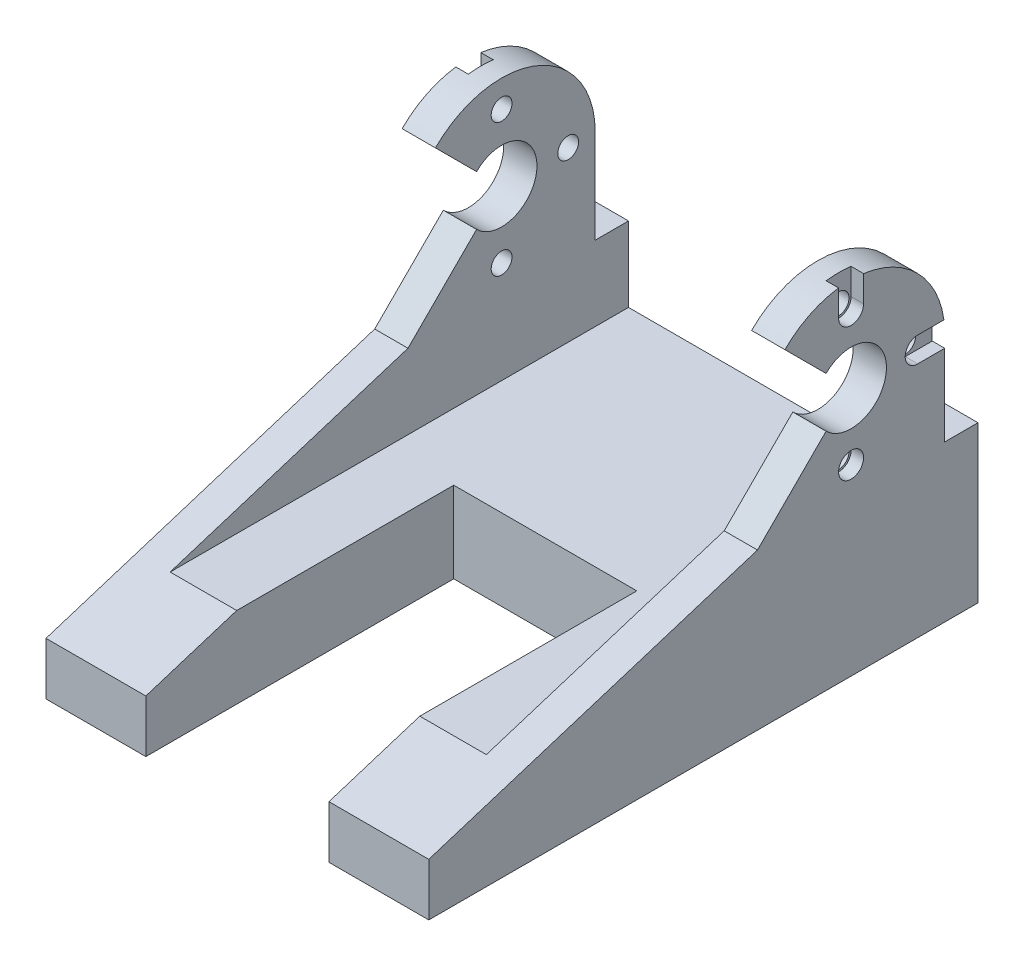
SolidWorks part; units mm, degrees
ref_plane "Front Plane" through (0, 0, 0) normal (0, 0, 1) x (1, 0, 0)
ref_plane "Top Plane" through (0, 0, 0) normal (0, 1, 0) x (1, 0, 0)
ref_plane "Right Plane" through (0, 0, 0) normal (1, 0, 0) x (0, 0, -1)
sketch "Sketch1" plane through (0, 0, 0) normal (0, 0, 1) x (1, 0, 0)
  line L1 (-25, 0) -> (25, 0)
  line L2 (-25, 0) -> (-25, -170)
  line L3 (-25, -170) -> (25, -170)
  line L4 (25, 0) -> (25, -170)
  dimension "D1" = 170
  dimension "D2" = 50
extrude "Boss-Extrude1" add sketch "Sketch1" against normal blind 55
sketch "Sketch2" plane through (0, 0, 0) normal (0, 0, 1) x (1, 0, 0)
  line L0 (25, 0) -> (-25, 0) construction
  line L1 (-17, 0) -> (17, 0)
  line L2 (-17, 0) -> (-17, -27)
  line L3 (-17, -27) -> (17, -27)
  line L4 (17, 0) -> (17, -27)
  line L5 (-25, 0) -> (-25, -170) construction
  dimension "D1" = 8
  dimension "D2" = 34
  dimension "D3" = 27
extrude "Cut-Extrude1" cut sketch "Sketch2" against normal through all
sketch "Sketch3" plane through (25, 0, 0) normal (1, 0, 0) x (0, 0, -1)
  line L0 (0, -170) -> (0, 0) construction
  line L1 (55, -27) -> (0, -27)
  line L2 (55, -27) -> (55, -24)
  line L3 (55, -24) -> (0, -24)
  line L4 (0, -27) -> (0, -24)
  line L5 (55, -170) -> (55, 0) construction
  line L7 (0, 0) -> (10, 0)
  line L8 (0, 0) -> (0, -24)
  line L9 (0, -24) -> (10, -24)
  line L10 (10, 0) -> (10, -24)
  line L11 (55, 0) -> (45, 0)
  line L12 (55, 0) -> (55, -24)
  line L13 (55, -24) -> (45, -24)
  line L14 (45, 0) -> (45, -24)
  circle A0 centre (27.5, -12.75) radius 10.25
  circle A1 centre (27.5, -12.75) radius 4.25
  circle A2 centre (27.5, -12.75) radius 8
  circle A3 centre (27.5, -4.75) radius 1
  circle A4 centre (35.5, -12.75) radius 1
  circle A5 centre (27.5, -20.75) radius 1
  circle A6 centre (19.5, -12.75) radius 1
  point P32 (27.5, -12.75)
  line M7 (0, 0) -> (0, -170)
  line M9 (55, -170) -> (55, 0)
  line M10 (55, 0) -> (0, 0)
  dimension "D2" = 11.25
  dimension "D3" = 27.5
  dimension "D4" = 20.5
  dimension "D7" = 8.5
  dimension "D8" = 16
  dimension "D9" = 4
  dimension "D1" = 3
  dimension "D5" = 10
  dimension "D6" = 10
extrude "Cut-Extrude2" cut sketch "Sketch3" against normal through all contours L14 L3 M10 M9 | L10 L3 M10 M7 | A2 A6 | A2 A6 | A1 | A2 A5 | A2 A5 | A2 A4 | A2 A4 | A2 A3 | A2 A3 region at (25, -12, -50) region at (25, -12, -5) region at (25, -12.75, -27.5) region at (25, -12.75, -35.0645) region at (25, -12.75, -35.913) region at (25, -5.1855, -27.5) region at (25, -4.337, -27.5) region at (25, -21.163, -27.5) region at (25, -20.3145, -27.5) region at (25, -12.75, -19.9355) region at (25, -12.75, -19.087)
sketch "Sketch4" plane through (0, 0, -10) normal (0, 0, 1) x (1, 0, 0)
  line L0 (-25, -24) -> (-17, -24) construction
  line L1 (-17, 0) -> (-19, 0)
  line L2 (-17, 0) -> (-17, -24)
  line L3 (-17, -24) -> (-19, -24)
  line L4 (-19, 0) -> (-19, -24)
  line L5 (0, 0) -> (0, -13.53) construction
  line L6 (19, 0) -> (19, -24)
  line L7 (17, -24) -> (19, -24)
  line L8 (17, 0) -> (17, -24)
  line L9 (17, 0) -> (19, 0)
  dimension "D1" = 2
extrude "Cut-Extrude3" cut sketch "Sketch4" against normal through all
sketch "Sketch5" plane through (25, 0, 0) normal (1, 0, 0) x (0, 0, -1)
  line L1 (10, 0) -> (45, 0)
  line L2 (10, 0) -> (10, -24)
  line L3 (10, -24) -> (45, -24)
  line L4 (45, 0) -> (45, -24)
  line L5 (38.75, -12.75) -> (38.75, -24)
  line L6 (16.25, -12.75) -> (10, -12.75)
  line L7 (16.25, -12.75) -> (16.25, -24)
  line L8 (16.25, -24) -> (10, -24)
  line L9 (10, -12.75) -> (10, -24)
  line L10 (38.75, -12.75) -> (45, -12.75)
  line L11 (38.75, -12.75) -> (38.75, -24)
  line L12 (38.75, -24) -> (45, -24)
  line L13 (45, -12.75) -> (45, -24)
  circle A0 centre (27.5, -12.75) radius 11.25
  line M8 (45, -24) -> (45, 0)
  line M9 (45, 0) -> (10, 0)
  line M10 (10, 0) -> (10, -24)
  dimension "D1" = 22.5
extrude "Cut-Extrude4" cut sketch "Sketch5" against normal through all contours A0 L10 L4 L6 M9 M10 | L7 L6 L2 L3 | L10 L5 L3 M8 region at (25, -0.3725, -27.5) region at (25, -18.375, -13.125) region at (25, -18.375, -41.875)
sketch "Sketch6" plane through (0, 0, 0) normal (0, 0, 1) x (1, 0, 0)
  line L1 (-19, -24) -> (19, -24)
  line L2 (-19, -24) -> (-19, -34)
  line L3 (-19, -34) -> (19, -34)
  line L4 (19, -24) -> (19, -34)
  dimension "D1" = 10
extrude "Cut-Extrude5" cut sketch "Sketch6" against normal through all
sketch "Sketch8" plane through (25, 0, 0) normal (1, 0, 0) x (0, 0, -1)
  line L0 (55, -170) -> (55, -24) construction
  line L1 (0, -170) -> (0, -24) construction
  line L2 (41.75, -132.5) -> (13.25, -132.5)
  line L3 (27.5, -132.5) -> (27.5, -179)
  line L4 (41.75, -179) -> (13.25, -179)
  line L5 (13.25, -132.5) -> (13.25, -179)
  line L7 (41.75, -132.5) -> (41.75, -179)
  line L11 (27.5, -167.75) -> (55, -167.75)
  line L12 (27.5, -167.75) -> (27.5, -170)
  line L13 (27.5, -170) -> (55, -170)
  line L14 (55, -167.75) -> (55, -170)
  line L16 (27.5, -167.75) -> (0, -167.75)
  line L17 (27.5, -167.75) -> (27.5, -170)
  line L18 (27.5, -170) -> (0, -170)
  line L19 (0, -167.75) -> (0, -170)
  circle A0 centre (27.5, -167.75) radius 10.25
  circle A1 centre (27.5, -12.75) radius 10.25
  line M4 (0, -24) -> (0, -170)
  line M5 (0, -170) -> (55, -170)
  line M6 (55, -170) -> (55, -24)
  dimension "D1" = 27.5
  dimension "D2" = 20.5
  dimension "D3" = 155
  dimension "D4" = 14.25
  dimension "D5" = 11.25
  dimension "D6" = 46.5
  dimension "D7" = 13.25
extrude "Cut-Extrude7" cut sketch "Sketch8" against normal through all contours A0 L3 L2 L5 L16 | A0 L11 L7 L2 L3 | L11 L7 M5 M6 | L5 L16 M4 M5 | A0 L16 L5 M5 | A0 L13 L7 L11 | L3 A0 L16 | L11 A0 L3 | L16 A0 L18 L3 | A0 L11 L3 M5 region at (25, -147.5157, -35.1704) region at (25, -147.5157, -19.8296) region at (25, -168.875, -48.375) region at (25, -168.8865, -39.7079) region at (25, -163.3998, -31.8502) region at (25, -163.3998, -23.1498) region at (25, -168.8704, -32.5838) region at (25, -168.8865, -15.2921) region at (25, -168.875, -6.625) region at (25, -168.8704, -22.4162)
sketch "Sketch9" plane through (0, 0, 0) normal (0, 0, 1) x (1, 0, 0)
  line L0 (-25, -167.75) -> (25, -167.75) construction
  line L1 (17, -167.75) -> (-17, -167.75)
  line L2 (17, -167.75) -> (17, -132.5)
  line L3 (17, -132.5) -> (-17, -132.5)
  line L4 (-17, -167.75) -> (-17, -132.5)
  line L5 (-25, -132.5) -> (25, -132.5) construction
  line L7 (-25, -24) -> (-25, -167.75) construction
  line L9 (25, -167.75) -> (25, -24) construction
  dimension "D1" = 8
  dimension "D2" = 8
extrude "Cut-Extrude8" cut sketch "Sketch9" against normal through all
sketch "Sketch11" plane through (25, 0, 0) normal (1, 0, 0) x (0, 0, -1)
  line L0 (27.5, -157.5) -> (27.5, -147.5)
  line L2 (27.5, -147.5) -> (55, -147.5)
  line L3 (27.5, -147.5) -> (27.5, -167.75)
  line L4 (27.5, -167.75) -> (55, -167.75)
  line L5 (55, -147.5) -> (55, -167.75)
  line L6 (27.5, -147.5) -> (0, -147.5)
  line L7 (27.5, -147.5) -> (27.5, -167.75)
  line L8 (27.5, -167.75) -> (0, -167.75)
  line L9 (0, -147.5) -> (0, -167.75)
  circle A0 centre (27.5, -167.75) radius 10.25
  arc A1 (38.75, -12.75) -> (16.25, -12.75) centre (27.5, -12.75) ccw construction
  line M1 (0, -167.75) -> (13.25, -167.75)
  line M2 (13.25, -167.75) -> (13.25, -132.5)
  line M4 (41.75, -132.5) -> (41.75, -167.75)
  line M5 (41.75, -167.75) -> (55, -167.75)
  line M6 (55, -167.75) -> (55, -24)
  line M12 (0, -24) -> (0, -167.75)
  dimension "D1" = 155
  dimension "D2" = 20.5
  dimension "D3" = 10
extrude "Cut-Extrude9" cut sketch "Sketch11" against normal through all contours A0 L0 L6 L8 M2 | A0 L4 L2 L0 M4 | L2 M4 M5 M6 | L6 M2 M12 M1 region at (25, -155.3124, -19.2638) region at (25, -155.3124, -35.7362) region at (25, -157.625, -48.375) region at (25, -157.625, -6.625)
sketch "Sketch12" plane through (25, 0, 0) normal (1, 0, 0) x (0, 0, -1)
  line L1 (13.25, -132.5) -> (41.75, -132.5)
  line L2 (13.25, -132.5) -> (13.25, -147.5)
  line L3 (13.25, -147.5) -> (41.75, -147.5)
  line L4 (41.75, -132.5) -> (41.75, -147.5)
extrude "Boss-Extrude2" add sketch "Sketch12" against normal blind 8
ref_plane "Plane1" through (0, 0, 0) normal (1, 0, 0) x (0, 0, -1)
mirror "Mirror1" about plane through (0, 0, 0) normal (1, 0, 0) of "Boss-Extrude2"
sketch "Sketch14" plane through (0, 0, 0) normal (0, 0, 1) x (1, 0, 0)
  line L0 (17, -148.55) -> (17, -158.75) construction
  line L1 (-17, -132.5) -> (17, -132.5)
  line L2 (-17, -132.5) -> (-17, -147.5)
  line L3 (-17, -147.5) -> (17, -147.5)
  line L4 (17, -132.5) -> (17, -147.5)
  line L5 (-17, -147.5) -> (17, -147.5)
  line L6 (-17, -147.5) -> (-17, -157.75)
  line L7 (-17, -157.75) -> (17, -157.75)
  line L8 (17, -147.5) -> (17, -157.75)
  line M11 (-17, -147.5) -> (-17, -132.5)
  line M12 (-17, -132.5) -> (17, -132.5)
  line M13 (17, -132.5) -> (17, -147.5)
  dimension "D1" = 10.25
extrude "Boss-Extrude3" add sketch "Sketch14" against normal blind 13.25 contours L3 M11 M13 M12 | L8 L3 L6 L7 region at (0, -140, 0) region at (0, -152.625, 0)
ref_plane "Plane2" through (0, 0, -27.5) normal (0, 0, 1) x (1, 0, 0)
mirror "Mirror2" about plane through (0, 0, -27.5) normal (0, 0, 1) of "Boss-Extrude3"
sketch "Sketch16" plane through (25, 0, 0) normal (1, 0, 0) x (0, 0, -1)
  line L0 (41.75, -132.5) -> (13.25, -132.5) construction
  line L1 (13.25, -132.5) -> (13.25, -147.5) construction
  circle A1 centre (16.5, -135.75) radius 2.5
  circle A2 centre (16.5, -135.75) radius 4.5
  circle A3 centre (38.5, -135.75) radius 4.5
  dimension "D1" = 3.25
  dimension "D2" = 3.25
  dimension "D3" = 2
extrude "Cut-Extrude13" cut sketch "Sketch16" against normal blind 8 contours A1 | A2 A1 | A3 region at (25, -135.75, -16.5) region at (25, -135.75, -12.1273) region at (25, -135.75, -38.5)
mirror "Mirror3" about plane through (0, 0, 0) normal (1, 0, 0) of "Cut-Extrude13"
sketch "Sketch17" plane through (25, 0, 0) normal (1, 0, 0) x (0, 0, -1)
  line L0 (55, -147.5) -> (55, -24) construction
  line L1 (27.5, -1.5) -> (55, -1.5)
  line L2 (27.5, -1.5) -> (27.5, -51.5)
  line L3 (27.5, -51.5) -> (55, -51.5)
  line L4 (55, -1.5) -> (55, -51.5)
  line L8 (55, -51.5) -> (0, -51.5)
  line L9 (55, -51.5) -> (55, -157.75)
  line L10 (55, -157.75) -> (0, -157.75)
  line L11 (0, -51.5) -> (0, -157.75)
  arc A0 (38.75, -12.75) -> (16.25, -12.75) centre (27.5, -12.75) ccw construction
  circle M2 centre (16.5, -135.75) radius 4.5
  circle M3 centre (38.5, -135.75) radius 4.5
  line M4 (0, -147.5) -> (55, -147.5)
  line M5 (55, -147.5) -> (55, -24)
  line M11 (0, -24) -> (0, -147.5)
  dimension "D1" = 50
extrude "Cut-Extrude15" cut sketch "Sketch17" against normal through all contours L3 L8 M11 M4 M5 M2 M3 | L11 L10 L9 M4 | M3 | M2 region at (25, -98.6049, -27.5) region at (25, -152.625, -27.5) region at (25, -135.75, -16.5) region at (25, -135.75, -38.5)
sketch "Sketch18" plane through (25, 0, 0) normal (1, 0, 0) x (0, 0, -1)
  line L1 (38.75, -24) -> (-71.25, -24)
  line L2 (38.75, -24) -> (38.75, -51.5)
  line L3 (38.75, -51.5) -> (-71.25, -51.5)
  line L4 (-71.25, -24) -> (-71.25, -51.5)
  line L6 (38.75, -24) -> (68.75, -24)
  line L7 (38.75, -24) -> (38.75, -51.5)
  line L8 (38.75, -51.5) -> (68.75, -51.5)
  line L9 (68.75, -24) -> (68.75, -51.5)
  line M8 (0, -24) -> (0, -51.5)
  line M9 (0, -51.5) -> (55, -51.5)
  line M10 (55, -51.5) -> (55, -24)
  line M11 (55, -24) -> (38.75, -24)
  line M15 (16.25, -24) -> (0, -24)
  dimension "D1" = 110
  dimension "D2" = 30
extrude "Boss-Extrude4" add sketch "Sketch18" against normal blind 50 contours L1 L4 L3 M8 | L9 L6 L8 M10 | L2 L1 M15 M8 M9 | L2 M11 M9 M10 region at (25, -37.75, -19.375) region at (25, -37.75, -46.875) region at (25, -37.75, -61.875) region at (25, -37.75, 35.625)
sketch "Sketch19" plane through (0, 0, 71.25) normal (0, 0, 1) x (1, 0, 0)
  line L1 (-19, -24) -> (19, -24)
  line L2 (-19, -24) -> (-19, -31)
  line L3 (-19, -31) -> (19, -31)
  line L4 (19, -24) -> (19, -31)
  dimension "D1" = 7
extrude "Cut-Extrude16" cut sketch "Sketch19" against normal through all
sketch "Sketch20" plane through (25, 0, 0) normal (1, 0, 0) x (0, 0, -1)
  line L1 (-71.25, -24) -> (68.75, -24)
  line L2 (-71.25, -24) -> (-71.25, -51.5)
  line L3 (-71.25, -51.5) -> (68.75, -51.5)
  line L4 (68.75, -24) -> (68.75, -51.5)
  line L5 (16.25, -24) -> (-13.75, -24)
  line L6 (16.25, -24) -> (16.25, -51.5)
  line L7 (16.25, -51.5) -> (-13.75, -51.5)
  line L8 (-13.75, -24) -> (-13.75, -51.5)
  line L10 (-13.75, -51.5) -> (-71.25, -51.5)
  line L11 (-13.75, -51.5) -> (-13.75, -24)
  line L12 (-13.75, -24) -> (-71.25, -24)
  line L13 (-71.25, -51.5) -> (-71.25, -24)
  line M8 (-71.25, -24) -> (-71.25, -51.5)
  line M9 (-71.25, -51.5) -> (68.75, -51.5)
  dimension "D1" = 30
extrude "Cut-Extrude17" cut sketch "Sketch20" against normal through all contours L8 L1 M8 M9 region at (25, -37.75, 42.5)
sketch "Sketch21" plane through (25, 0, 0) normal (1, 0, 0) x (0, 0, -1)
  line L0 (16.25, -24) -> (-13.75, -51.5)
  line L1 (16.25, -24) -> (-13.75, -24)
  line L2 (16.25, -24) -> (16.25, -51.5)
  line L3 (16.25, -51.5) -> (-13.75, -51.5)
  line L4 (-13.75, -24) -> (-13.75, -51.5)
  line M6 (16.25, -24) -> (-13.75, -24)
  line M7 (-13.75, -24) -> (-13.75, -51.5)
extrude "Cut-Extrude18" cut sketch "Sketch21" against normal through all contours L0 M6 M7 region at (25, -33.1667, 3.75)
sketch "Sketch22" plane through (25, 0, 0) normal (1, 0, 0) x (0, 0, -1)
  line L3 (68.75, -51.5) -> (-13.75, -51.5)
  line L4 (68.75, -51.5) -> (68.75, -54)
  line L5 (68.75, -54) -> (-13.75, -54)
  line L6 (-13.75, -51.5) -> (-13.75, -54)
  dimension "D1" = 2.5
extrude "Boss-Extrude5" add sketch "Sketch22" against normal blind 50
sketch "Sketch24" plane through (25, 0, 0) normal (1, 0, 0) x (0, 0, -1)
  line L1 (68.75, -24) -> (46.75, -24)
  line L2 (68.75, -24) -> (68.75, -41)
  line L3 (68.75, -41) -> (46.75, -41)
  line L4 (46.75, -24) -> (46.75, -41)
  dimension "D1" = 17
  dimension "D2" = 22
extrude "Cut-Extrude19" cut sketch "Sketch24" against normal through all
sketch "Sketch25" plane through (0, -31, 0) normal (0, 1, 0) x (1, 0, 0)
  line L1 (-19, 46.75) -> (19, 46.75)
  line L2 (-19, 46.75) -> (-19, 8.6136)
  line L3 (-19, 8.6136) -> (19, 8.6136)
  line L4 (19, 46.75) -> (19, 8.6136)
extrude "Cut-Extrude20" cut sketch "Sketch25" against normal blind 10
sketch "Sketch27" plane through (0, -41, 0) normal (0, 1, 0) x (1, 0, 0)
  line L0 (-25, 68.75) -> (25, 68.75) construction
  line L1 (19, 8.6136) -> (-19, 8.6136)
  line L2 (19, 8.6136) -> (19, 68.75)
  line L3 (19, 68.75) -> (-19, 68.75)
  line L4 (-19, 8.6136) -> (-19, 68.75)
extrude "Boss-Extrude6" add sketch "Sketch27" along normal blind 8.6
sketch "Sketch29" plane through (0, 0, -8.6136) normal (0, 0, -1) x (-1, 0, 0)
  line L1 (-19, -31) -> (19, -31)
  line L2 (-19, -31) -> (-19, -32.4)
  line L3 (-19, -32.4) -> (19, -32.4)
  line L4 (19, -31) -> (19, -32.4)
extrude "Cut-Extrude21" cut sketch "Sketch29" against normal through all
sketch "Sketch30" plane through (-25, 0, 0) normal (-1, 0, 0) x (0, 0, 1)
  line L0 (-68.75, -32.4) -> (-68.75, -41) construction
  line L1 (-38.75, -24) -> (31.25, -24)
  line L2 (-38.75, -24) -> (-38.75, -53.9144)
  line L3 (-38.75, -53.9144) -> (31.25, -53.9144)
  line L4 (31.25, -24) -> (31.25, -53.9144)
  line L5 (-16.25, -24) -> (31.25, -38.9572)
  line L6 (31.25, -38.9572) -> (31.25, -53.9144)
  line L7 (-16.25, -24) -> (-16.25, -32.4)
  line L8 (-46.75, -32.4) -> (-7.0864, -32.4) construction
  line L9 (-16.25, -32.4) -> (-7.0864, -32.4)
  line L10 (-7.0864, -32.4) -> (-16.25, -24)
  line M5 (13.75, -54) -> (13.75, -51.5)
  line M6 (13.75, -51.5) -> (-16.25, -24)
  dimension "D1" = 100
extrude "Boss-Extrude7" add sketch "Sketch30" against normal blind 50 contours L5 L3 L4 M6 M5 | L7 L9 L10 region at (-25, -40.9436, 13.5151)
sketch "Sketch31" plane through (0, 0, -68.75) normal (0, 0, -1) x (-1, 0, 0)
  line L1 (-19, -24) -> (19, -24)
  line L2 (-19, -24) -> (-19, -41)
  line L3 (-19, -41) -> (19, -41)
  line L4 (19, -24) -> (19, -41)
extrude "Cut-Extrude22" cut sketch "Sketch31" against normal through all
sketch "Sketch32" plane through (25, 0, 0) normal (1, 0, 0) x (0, 0, -1)
  line L0 (-31.25, -38.9572) -> (-31.25, -53.9144) construction
  line L1 (68.75, -54) -> (-31.25, -54)
  line L2 (68.75, -54) -> (68.75, -51)
  line L3 (68.75, -51) -> (-31.25, -51)
  line L4 (-31.25, -54) -> (-31.25, -51)
  dimension "D1" = 3
extrude "Cut-Extrude23" cut sketch "Sketch32" against normal through all
sketch "Sketch33" plane through (0, -41, 0) normal (0, 1, 0) x (1, 0, 0)
  line L0 (19, -31.25) -> (-19, -31.25) construction
  line L1 (11, -31.25) -> (-11, -31.25)
  line L2 (11, -31.25) -> (11, 13.75)
  line L3 (11, 13.75) -> (-11, 13.75)
  line L4 (-11, -31.25) -> (-11, 13.75)
  line L6 (-25, 68.75) -> (-10, 68.75)
  line L7 (-25, 68.75) -> (-25, 46.75)
  line L8 (-25, 46.75) -> (-10, 46.75)
  line L9 (-10, 68.75) -> (-10, 46.75)
  line L10 (25, 68.75) -> (10, 68.75)
  line L11 (25, 68.75) -> (25, 46.75)
  line L12 (25, 46.75) -> (10, 46.75)
  line L13 (10, 68.75) -> (10, 46.75)
  line L15 (19, 16.25) -> (19, -31.25) construction
  line L16 (-19, -31.25) -> (-19, 46.75) construction
  line L18 (-10, 68.75) -> (10, 68.75)
  line L19 (-10, 68.75) -> (-10, 58.75)
  line L20 (-10, 58.75) -> (10, 58.75)
  line L21 (10, 68.75) -> (10, 58.75)
  line M10 (-25, 46.75) -> (-19, 46.75)
  line M12 (-19, -31.25) -> (19, -31.25)
  line M14 (19, 46.75) -> (25, 46.75)
  line M15 (25, 46.75) -> (25, 68.75)
  line M16 (25, 68.75) -> (-25, 68.75)
  line M17 (-25, 68.75) -> (-25, 46.75)
  dimension "D1" = 8
  dimension "D2" = 8
  dimension "D3" = 45
  dimension "D4" = 15
  dimension "D5" = 15
  dimension "D6" = 10
extrude "Cut-Extrude24" cut sketch "Sketch33" against normal through all contours L9 L8 M16 M17 M10 | L13 L12 M16 M14 M15 | L9 L20 L13 M16 | L4 L2 L3 M12 region at (0, -41, 8.75) region at (-17.5, -41, -57.75) region at (0, -41, -63.75) region at (17.5, -41, -57.75)
sketch "Sketch34" plane through (0, -41, 0) normal (0, 1, 0) x (1, 0, 0)
  line L0 (-10, 58.75) -> (10, 58.75) construction
  line L1 (-4, 58.75) -> (4, 58.75)
  line L2 (-4, 58.75) -> (-4, 46.75)
  line L3 (-4, 46.75) -> (4, 46.75)
  line L4 (4, 58.75) -> (4, 46.75)
  line L5 (-10, 58.75) -> (-10, 46.75) construction
  line L6 (10, 58.75) -> (10, 46.75) construction
  dimension "D1" = 6
  dimension "D2" = 6
  dimension "D3" = 12
extrude "Cut-Extrude25" cut sketch "Sketch34" against normal through all
sketch "Sketch36" plane through (0, -41, 0) normal (0, 1, 0) x (1, 0, 0)
  line L1 (19, -31.25) -> (-19, -31.25)
  line L2 (19, -31.25) -> (19, 58.75)
  line L3 (19, 58.75) -> (-19, 58.75)
  line L4 (-19, -31.25) -> (-19, 58.75)
  line L5 (-4, 58.75) -> (4, 58.75)
  line L6 (-4, 58.75) -> (-4, 46.75)
  line L7 (-4, 46.75) -> (4, 46.75)
  line L8 (4, 58.75) -> (4, 46.75)
  line L9 (10, 58.75) -> (19, 58.75)
  line L10 (10, 58.75) -> (10, 46.75)
  line L11 (10, 46.75) -> (19, 46.75)
  line L12 (19, 58.75) -> (19, 46.75)
  line L13 (-10, 58.75) -> (-19, 58.75)
  line L14 (-10, 58.75) -> (-10, 46.75)
  line L15 (-10, 46.75) -> (-19, 46.75)
  line L16 (-19, 58.75) -> (-19, 46.75)
  line L17 (-11, 13.75) -> (11, 13.75)
  line L18 (-11, 13.75) -> (-11, -31.25)
  line L19 (-11, -31.25) -> (11, -31.25)
  line L20 (11, 13.75) -> (11, -31.25)
  line M1 (4, 46.75) -> (-4, 46.75)
  line M2 (-4, 46.75) -> (-4, 58.75)
  line M3 (-4, 58.75) -> (-10, 58.75)
  line M4 (-10, 58.75) -> (-10, 46.75)
  line M5 (-10, 46.75) -> (-19, 46.75)
  line M6 (-19, 46.75) -> (-19, -31.25)
  line M7 (-19, -31.25) -> (-11, -31.25)
  line M8 (-11, -31.25) -> (-11, 13.75)
  line M9 (-11, 13.75) -> (11, 13.75)
  line M10 (11, 13.75) -> (11, -31.25)
  line M11 (11, -31.25) -> (19, -31.25)
  line M12 (19, -31.25) -> (19, 46.75)
  line M13 (19, 46.75) -> (10, 46.75)
  line M14 (10, 46.75) -> (10, 58.75)
  line M15 (10, 58.75) -> (4, 58.75)
  line M16 (4, 58.75) -> (4, 46.75)
extrude "Boss-Extrude8" add sketch "Sketch36" along normal blind 8 contours M16 M1 M2 M3 M4 M5 M6 M7 M8 M9 M10 M11 M12 M13 M14 M15 region at (0, -41, -18.522)
sketch "Sketch37" plane through (25, 0, 0) normal (1, 0, 0) x (0, 0, -1)
  line L0 (-31.25, -38.9572) -> (-31.25, -51) construction
  line L1 (58.75, -51) -> (-31.25, -51)
  line L2 (58.75, -51) -> (58.75, -42)
  line L3 (58.75, -42) -> (-31.25, -42)
  line L4 (-31.25, -51) -> (-31.25, -42)
  line L5 (-31.25, -38.9572) -> (-12.3315, -33)
  line L6 (-12.3315, -33) -> (-31.25, -33)
  line L7 (-12.3315, -33) -> (-12.3315, -38.9572)
  line L8 (-12.3315, -38.9572) -> (-31.25, -38.9572)
  line L9 (-31.25, -33) -> (-31.25, -38.9572)
  line L11 (58.75, -42) -> (46.75, -42)
  line L12 (58.75, -42) -> (58.75, -51)
  line L13 (58.75, -51) -> (46.75, -51)
  line L14 (46.75, -42) -> (46.75, -51)
  line M7 (-31.25, -51) -> (46.75, -51)
  line M8 (46.75, -51) -> (46.75, -24)
  line M13 (16.25, -24) -> (-31.25, -38.9572)
  line M14 (-31.25, -38.9572) -> (-31.25, -51)
  dimension "D1" = 9
extrude "Cut-Extrude27" cut sketch "Sketch37" against normal through all contours L3 M8 M14 M7 | L6 L9 M13 | L2 L3 L1 M8 region at (25, -34.9857, 24.9438) region at (25, -46.5, -52.75) region at (25, -46.5, -7.75)
fillet "Fillet1" radius 10 2 edges at (-7, -42, -58.75) (7, -42, -58.75)
sketch "Sketch38" plane through (0, 0, 0) normal (0, 1, 0) x (1, 0, 0)
  line L6 (-11, -31.25) -> (-25, -31.25) construction
  line L7 (-25, 46.75) -> (-23, 46.75)
  line L8 (-25, 46.75) -> (-25, -31.25)
  line L9 (-25, -31.25) -> (-23, -31.25)
  line L10 (-23, 46.75) -> (-23, -31.25)
  line L11 (25, -31.25) -> (11, -31.25) construction
  line L12 (25, 46.75) -> (23, 46.75)
  line L13 (25, 46.75) -> (25, -31.25)
  line L14 (25, -31.25) -> (23, -31.25)
  line L15 (23, 46.75) -> (23, -31.25)
  line L17 (-23, -31.25) -> (23, -31.25)
  line L18 (-23, -31.25) -> (-23, -23.25)
  line L19 (-23, -23.25) -> (23, -23.25)
  line L20 (23, -31.25) -> (23, -23.25)
  dimension "D1" = 2
  dimension "D2" = 2
  dimension "D3" = 8
extrude "Cut-Extrude29" cut sketch "Sketch38" against normal through all both and the other way through all contours L10 L7 L8 L9 | L12 L15 L14 L13 | L19 L10 L17 L15 region at (-24, 0, -7.75) region at (0, 0, 27.25) region at (24, 0, -7.75)
sketch "Sketch39" plane through (23, 0, 0) normal (1, 0, 0) x (0, 0, -1)
  line L0 (46.75, -24) -> (38.75, -24) construction
  line L1 (42.75, -24) -> (64.9734, -24)
  line L2 (42.75, -24) -> (42.75, -43.4413)
  line L3 (42.75, -43.4413) -> (64.9734, -43.4413)
  line L4 (64.9734, -24) -> (64.9734, -43.4413)
extrude "Cut-Extrude30" cut sketch "Sketch39" against normal through all
sketch "Sketch41" plane through (0, -42, 0) normal (0, -1, 0) x (1, 0, 0)
  line L1 (-23, 23.25) -> (23, 23.25)
  line L2 (-23, 23.25) -> (-23, -42.75)
  line L3 (-23, -42.75) -> (23, -42.75)
  line L4 (23, 23.25) -> (23, -42.75)
  line L5 (-11, 23.25) -> (11, 23.25)
  line L6 (-11, 23.25) -> (-11, -13.75)
  line L7 (-11, -13.75) -> (11, -13.75)
  line L8 (11, 23.25) -> (11, -13.75)
  line M1 (-23, 23.25) -> (-23, -42.75)
  line M2 (-23, -42.75) -> (23, -42.75)
  line M3 (23, -42.75) -> (23, 23.25)
  line M4 (23, 23.25) -> (11, 23.25)
  line M5 (11, 23.25) -> (11, -13.75)
  line M6 (11, -13.75) -> (-11, -13.75)
  line M7 (-11, -13.75) -> (-11, 23.25)
  line M8 (-11, 23.25) -> (-23, 23.25)
extrude "Boss-Extrude9" add sketch "Sketch41" along normal blind 0.75 contours M8 M1 M2 M3 M4 M5 M6 M7 region at (0, -42, -15.0619)
sketch "Sketch42" plane through (23, 0, 0) normal (1, 0, 0) x (0, 0, -1)
  line L0 (16.25, -24) -> (27.5, -12.75)
  line L1 (27.5, -12.75) -> (19.545, -4.795)
  line L2 (19.545, -4.795) -> (8.295, -16.045)
  line L3 (8.295, -16.045) -> (16.25, -24)
  arc A0 (38.75, -12.75) -> (16.25, -12.75) centre (27.5, -12.75) ccw construction
extrude "Cut-Extrude31" cut sketch "Sketch42" against normal through all
sketch "Sketch44" plane through (23, 0, 0) normal (1, 0, 0) x (0, 0, -1)
  circle A0 centre (27.5, -4.75) radius 1.25
  circle A1 centre (27.5, -12.75) radius 8
  circle A2 centre (35.5, -12.75) radius 1.25
  circle A3 centre (27.5, -20.75) radius 1.25
  circle A4 centre (19.5, -12.75) radius 1.25
  point P15 (27.5, -12.75)
  circle M11 centre (35.5, -12.75) radius 1
  circle M12 centre (27.5, -4.75) radius 1
  circle M13 centre (27.5, -20.75) radius 1
  dimension "D1" = 2.5
  dimension "D2" = 4
extrude "Cut-Extrude32" cut sketch "Sketch44" against normal through all contours A1 A2 M11 | A1 A2 M11 | A0 A1 M12 | A1 A0 M12 | A1 A3 M13 | A1 A3 M13 region at (23, -4.7978, -28.7207) region at (23, -4.8564, -26.3816) region at (23, -11.8531, -36.3294) region at (23, -11.6316, -35.3936) region at (23, -19.5276, -27.5) region at (23, -20.699, -26.3738)
sketch "Sketch45" plane through (23, 0, 0) normal (1, 0, 0) x (0, 0, -1)
  line L1 (26, -4.75) -> (29, -4.75)
  line L2 (26, -4.75) -> (26, -1.0228)
  line L3 (26, -1.0228) -> (29, -1.0228)
  line L4 (29, -4.75) -> (29, -1.0228)
  line L5 (35.5, -11.25) -> (40.1611, -11.25)
  line L6 (35.5, -11.25) -> (35.5, -14.25)
  line L7 (35.5, -14.25) -> (40.1611, -14.25)
  line L8 (40.1611, -11.25) -> (40.1611, -14.25)
  circle A0 centre (27.5, -4.75) radius 1.5
  circle A1 centre (27.5, -12.75) radius 8
  circle A2 centre (35.5, -12.75) radius 1.5
  circle A3 centre (27.5, -20.75) radius 1.5
  circle A4 centre (19.5, -12.75) radius 1.5
  point P16 (27.5, -12.75)
  circle M1 centre (35.5, -12.75) radius 1.25
  circle M2 centre (27.5, -4.75) radius 1.25
  circle M3 centre (27.5, -20.75) radius 1.25
  arc M4 (38.75, -12.75) -> (19.545, -4.795) centre (27.5, -12.75) ccw
  line M13 (38.75, -24) -> (38.75, -12.75)
  dimension "D1" = 4
extrude "Cut-Extrude33" cut sketch "Sketch45" against normal blind 1.5 contours A0 L4 L2 M4 | A2 L7 L5 M13 M4 | A0 A1 M2 | L1 A0 M2 | A1 A0 L1 M2 | A1 L1 A0 M2 | L6 A2 M1 | L6 A2 A1 M1 | A1 A2 M1 | A1 A2 L6 M1 | A1 A3 M3 | A1 A3 M3 region at (23, -3.4665, -27.5) region at (23, -4.8099, -28.8808) region at (23, -2.5799, -27.5) region at (23, -4.8099, -26.1192) region at (23, -4.9007, -28.8643) region at (23, -12.7592, -37.6786) region at (23, -11.3692, -35.4401) region at (23, -11.3857, -35.3493) region at (23, -11.7131, -36.5369) region at (23, -14.1308, -35.4401) region at (23, -20.6812, -28.9642) region at (23, -20.5993, -28.8643)
ref_plane "Plane3" through (0, 0, 0) normal (1, 0, 0) x (0, 0, -1)
mirror "Mirror4" about plane through (0, 0, 0) normal (1, 0, 0) of "Cut-Extrude33"
